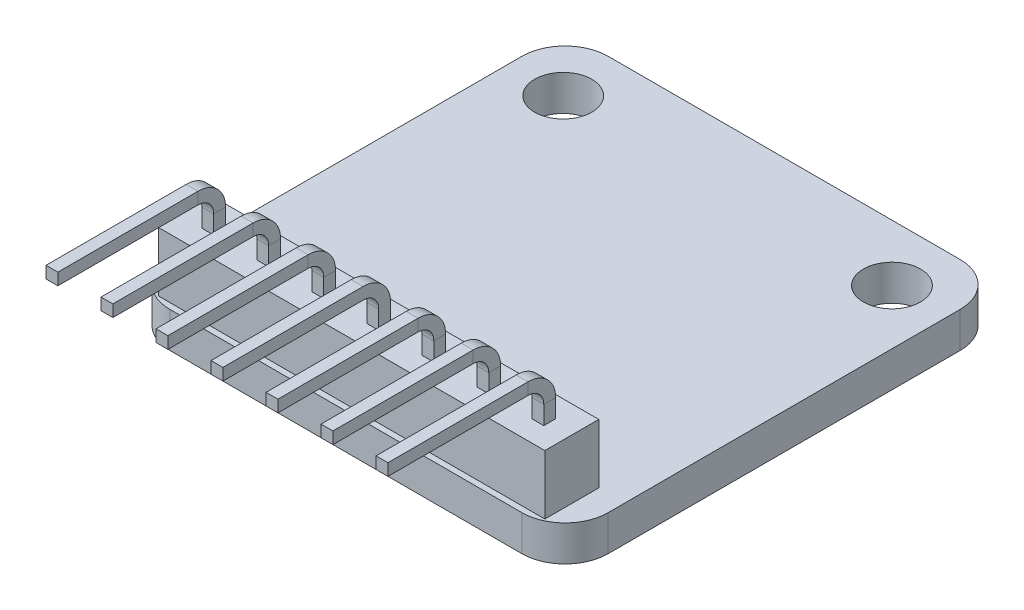
SolidWorks part; units mm, degrees
ref_plane "Front Plane" through (0, 0, 0) normal (0, 0, 1) x (1, 0, 0)
ref_plane "Top Plane" through (0, 0, 0) normal (0, 1, 0) x (1, 0, 0)
ref_plane "Right Plane" through (0, 0, 0) normal (1, 0, 0) x (0, 0, -1)
sketch "Sketch2" plane through (0, 0, 0) normal (0, 1, 0) x (1, 0, 0)
  line L0 (2.54, 17.695) -> (17.78, 17.695) construction
  line L1 (0, 0) -> (20.32, 0)
  line L2 (0, 0) -> (0, 20.32)
  line L3 (0, 20.32) -> (20.32, 20.32)
  line L4 (20.32, 0) -> (20.32, 20.32)
  circle A0 centre (2.54, 17.695) radius 1.325
  circle A1 centre (17.78, 17.695) radius 1.325
  point P7 (10.16, 17.695)
  point P8 (10.16, 20.32)
  dimension "D4" = 2.65
  dimension "D1" = 20.32
  dimension "D2" = 20.32
  dimension "D3" = 15.24
  dimension "D5" = 1.3
extrude "Boss-Extrude1" add sketch "Sketch2" along normal blind 1.65
sketch "Sketch3" plane through (0, 1.65, 0) normal (0, 1, 0) x (1, 0, 0)
  line L0 (0, 0) -> (20.32, 0) construction
  line L1 (9.885, 1.249) -> (10.435, 1.249)
  line L2 (9.885, 1.249) -> (9.885, 1.799)
  line L3 (9.885, 1.799) -> (10.435, 1.799)
  line L4 (10.435, 1.249) -> (10.435, 1.799)
  line L5 (9.885, 1.249) -> (10.435, 1.799) construction
  line L6 (9.885, 1.799) -> (10.435, 1.249) construction
  point P0 (10.16, 1.524)
  point P10 (10.16, 0)
  dimension "D1" = 0.55
  dimension "D2" = 1.524
sketch "Sketch4" plane through (0, 0, 0) normal (1, 0, 0) x (0, 0, -1)
  line L0 (1.524, 1.65) -> (1.524, 5.25)
  line L1 (0.524, 6.25) -> (-5.976, 6.25)
  arc A0 (1.524, 5.25) -> (0.524, 6.25) centre (0.524, 5.25) ccw
  point P6 (1.524, 6.25)
  dimension "D3" = 1
  dimension "D1" = 4.6
  dimension "D2" = 7.5
sweep "Sweep1" add profiles "Sketch3" path "Sketch4"
pattern_linear "LPattern1" count 4 spacing 2.55 along (-1, 0, 0) count 4 spacing 2.55 along (1, 0, 0) of "Sweep1"
sketch "Sketch5" plane through (0, 1.65, 0) normal (0, 1, 0) x (1, 0, 0)
  line L0 (2.235, 1.799) -> (2.235, 1.249) construction
  line L1 (1.21, 0.274) -> (19.11, 0.274)
  line L2 (1.21, 0.274) -> (1.21, 2.774)
  line L3 (1.21, 2.774) -> (19.11, 2.774)
  line L4 (19.11, 0.274) -> (19.11, 2.774)
  line L5 (0, 0) -> (20.32, 0) construction
  point P6 (2.235, 1.524)
  point P7 (1.21, 1.524)
  point P10 (10.16, 0)
  point P11 (10.16, 0.274)
  dimension "D1" = 17.9
  dimension "D2" = 2.5
extrude "Boss-Extrude2" add sketch "Sketch5" along normal blind 2.75
sketch "Sketch6" plane through (0, 0, 0) normal (0, -1, 0) x (1, 0, 0)
  line L0 (0, -20.32) -> (0, 0) construction
  line L1 (8.906, -8.656) -> (10.906, -8.656)
  line L2 (8.906, -8.656) -> (8.906, -11.156)
  line L3 (8.906, -11.156) -> (10.906, -11.156)
  line L4 (10.906, -8.656) -> (10.906, -11.156)
  line L5 (8.906, -8.656) -> (10.906, -11.156) construction
  line L6 (8.906, -11.156) -> (10.906, -8.656) construction
  line L7 (11.958, -8.656) -> (14.458, -8.656)
  line L8 (11.958, -8.656) -> (11.958, -12.156)
  line L9 (11.958, -12.156) -> (14.458, -12.156)
  line L10 (14.458, -8.656) -> (14.458, -12.156)
  line L11 (11.958, -8.656) -> (14.458, -12.156) construction
  line L12 (11.958, -12.156) -> (14.458, -8.656) construction
  line L13 (20.32, -20.32) -> (0, -20.32) construction
  point P0 (9.906, -9.906)
  point P5 (13.208, -10.406)
  dimension "D1" = 3.302
  dimension "D2" = 9.906
  dimension "D3" = 10.414
  dimension "D4" = 2
  dimension "D5" = 2.5
  dimension "D6" = 2.5
  dimension "D7" = 3.5
extrude "Boss-Extrude3" add sketch "Sketch6" along normal blind 0.5
fillet "Fillet1" radius 2 4 edges at (0, 0.825, 0) (0, 0.825, -20.32) (20.32, 0.825, -20.32) (20.32, 0.825, 0)
sketch "Sketch7" plane through (0, -0.5, 0) normal (0, -1, 0) x (1, 0, 0)
  line L8 (14.058, -11.756) -> (14.058, -9.056)
  line L9 (14.058, -9.056) -> (12.358, -9.056)
  line L10 (12.358, -9.056) -> (12.358, -11.756)
  line L11 (12.358, -11.756) -> (14.058, -11.756)
  line L12 (14.058, -11.756) -> (14.058, -9.056)
  line L13 (14.058, -9.056) -> (12.358, -9.056)
  line L14 (12.358, -9.056) -> (12.358, -11.756)
  line L15 (12.358, -11.756) -> (14.058, -11.756)
  dimension "D1" = 0.4
extrude "Cut-Extrude1" cut sketch "Sketch7" against normal blind 0.1
equation "\"width\"= 24"
equation "\"thk\"= 3"
equation "\"holesize\"= 4.2"
equation "\"holedistance\"= ( 20 + 12 ) / 2"
equation "\"threaded_hole\"= 3.9"
equation "\"fillet_radius\"= 2"
equation "\"ground_clearance\"= 25"
equation "\"tire_thk\"= 4"
equation "\"innerwheel_diam\" = \"wheel_diam\"-2*\"tire_thk\""
equation "\"innerwheel_thk\"= 8"
equation "\"wheel_diam\"= 2*(\"width\"/2+\"ground_clearance\")"
equation "\"coloursensor_holesize\"= 2.65"
equation "\"D4@Sketch2\"=\"coloursensor_holesize\""
